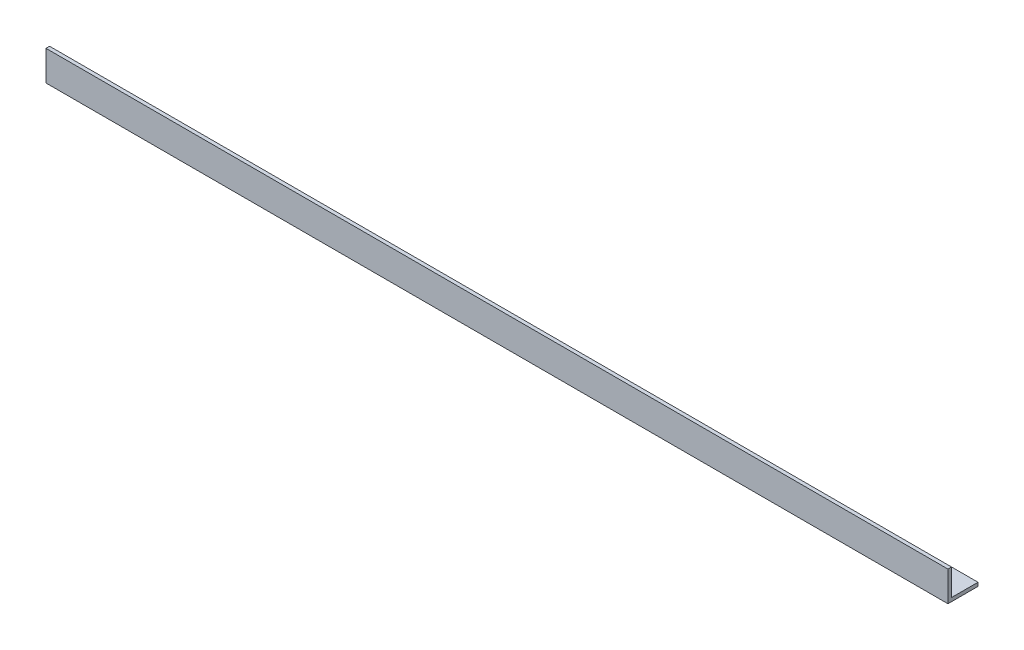
SolidWorks part; units mm, degrees
ref_plane "Спереди" through (0, 0, 0) normal (0, 0, 1) x (1, 0, 0)
ref_plane "Сверху" through (0, 0, 0) normal (0, 1, 0) x (1, 0, 0)
ref_plane "Справа" through (0, 0, 0) normal (1, 0, 0) x (0, 0, -1)
sketch "Эскиз1" plane through (0, 0, 0) normal (1, 0, 0) x (0, 0, -1)
  line L0 (0, 0) -> (50, 0)
  line L5 (0, 50) -> (0, 0)
extrude "Вытянуть-Тонкостенный2" add sketch "Эскиз1" along normal blind 1500 thin thin type one direction reverse wall 6
